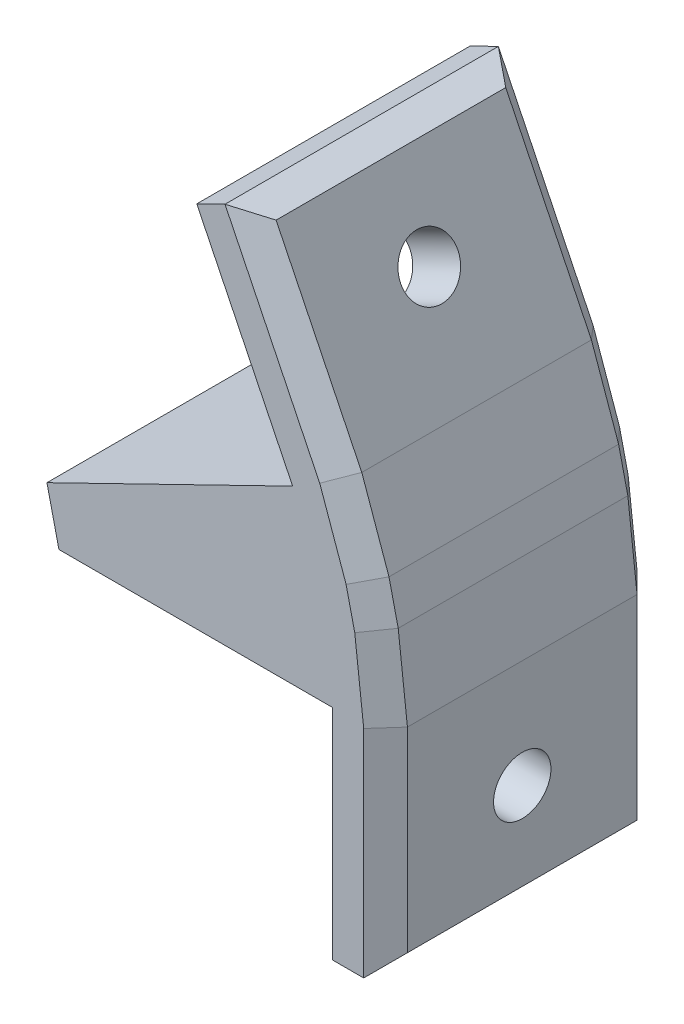
SolidWorks part; units mm, degrees
ref_plane "Plan de face" through (0, 0, 0) normal (0, 0, 1) x (1, 0, 0)
ref_plane "Plan de dessus" through (0, 0, 0) normal (0, 1, 0) x (1, 0, 0)
ref_plane "Plan de droite" through (0, 0, 0) normal (1, 0, 0) x (0, 0, -1)
sketch "Esquisse1" plane through (0, 0, 0) normal (0, 0, 1) x (1, 0, 0)
  line L0 (0, 0) -> (20, 0)
  line L1 (20, 0) -> (17.9759, 8.7674)
  line L2 (17.9759, 8.7674) -> (0, 0)
  dimension "D1" = 20
  dimension "D2" = 20
  dimension "D3" = 26
extrude "Boss.-Extru.1" add sketch "Esquisse1" along normal blind 20
sketch "Esquisse2" plane through (0, 0, 0) normal (-0.4384, 0.8988, 0) x (0.8988, 0.4384, 0)
  line L1 (0, -20) -> (20, -20)
  line L2 (0, -20) -> (0, 0)
  line L3 (0, 0) -> (20, 0)
  line L4 (20, -20) -> (20, 0)
extrude "Boss.-Extru.2" add sketch "Esquisse2" along normal blind 2
sketch "Esquisse3" plane through (0, 0, 0) normal (0, -1, 0) x (1, 0, 0)
  line L1 (0, 20) -> (20, 20)
  line L2 (0, 20) -> (0, 0)
  line L3 (0, 0) -> (20, 0)
  line L4 (20, 20) -> (20, 0)
extrude "Boss.-Extru.3" add sketch "Esquisse3" along normal blind 2
sketch "Esquisse4" plane through (18.9879, 4.3837, 0) normal (0.9744, 0.225, 0) x (0, 0, -1)
  line L1 (-20, 4.499) -> (0, 4.499)
  line L2 (-20, 4.499) -> (-20, -4.499)
  line L3 (-20, -4.499) -> (0, -4.499)
  line L4 (0, 4.499) -> (0, -4.499)
extrude "Boss.-Extru.4" add sketch "Esquisse4" along normal blind 4
sketch "Esquisse5" plane through (0, 0, 20) normal (0, 0, 1) x (1, 0, 0)
  line L0 (17.0991, 10.565) -> (10.0852, 24.9457)
  line L1 (10.0852, 24.9457) -> (13.5882, 26.6543)
  line L2 (13.5882, 26.6543) -> (21.8734, 9.6672)
  line L3 (21.8734, 9.6672) -> (17.9759, 8.7674)
  line L4 (17.9759, 8.7674) -> (17.0991, 10.565)
  line L5 (20, 0) -> (20, -2)
  line L6 (20, -2) -> (20, -18)
  line L7 (20, -18) -> (23.8975, -18)
  line L8 (23.8975, -18) -> (23.8975, 0.8998)
  line L9 (23.8975, 0.8998) -> (20, 0)
  dimension "D1" = 16
  dimension "D2" = 16
extrude "Boss.-Extru.5" add sketch "Esquisse5" against normal blind 20
chamfer "Chanfrein1" distance 3 distance2 3 2 edges at (23.8975, 0.8998, 10) (21.8734, 9.6672, 10)
chamfer "Chanfrein2" distance 1.6 angle 45 12 edges at (23.8975, -18, 10) (23.8975, -10.0501, 0) (23.5601, 0.8614, 0) (22.8854, 5.2835, 0) (21.5532, 9.5539, 0) (17.0732, 19.5089, 0) (13.5882, 26.6543, 10) (17.0732, 19.5089, 20) (21.5532, 9.5539, 20) (22.8854, 5.2835, 20) (23.5601, 0.8614, 20) (23.8975, -10.0501, 20)
sketch "Esquisse7" plane through (17.9759, 8.7674, 0) normal (-0.8988, -0.4384, 0) x (0, 0, 1)
  line L0 (0, 18) -> (20, 18) construction
  line L1 (20, 18) -> (20, 2) construction
  circle A0 centre (10, 10) radius 2.1
  dimension "D1" = 4.2
  dimension "D2" = 8
  dimension "D3" = 10
extrude "Enlèv. mat.-Extru.1" cut sketch "Esquisse7" against normal through all
sketch "Esquisse8" plane through (20, 0, 0) normal (-1, 0, 0) x (0, 0, 1)
  line L0 (0, -2) -> (0, -18) construction
  line L1 (0, -18) -> (20, -18) construction
  circle A0 centre (10, -10) radius 2.1
  dimension "D1" = 4.2
  dimension "D2" = 10
  dimension "D3" = 8
extrude "Enlèv. mat.-Extru.2" cut sketch "Esquisse8" against normal through all
sketch "Esquisse9" plane through (0, 0, 20) normal (0, 0, 1) x (1, 0, 0)
  line L0 (-0.8767, 1.7976) -> (0, 0)
  line L1 (0, 0) -> (0, -2)
  line L2 (0, -2) -> (-0.8767, 1.7976)
extrude "Boss.-Extru.6" add sketch "Esquisse9" against normal blind 20
